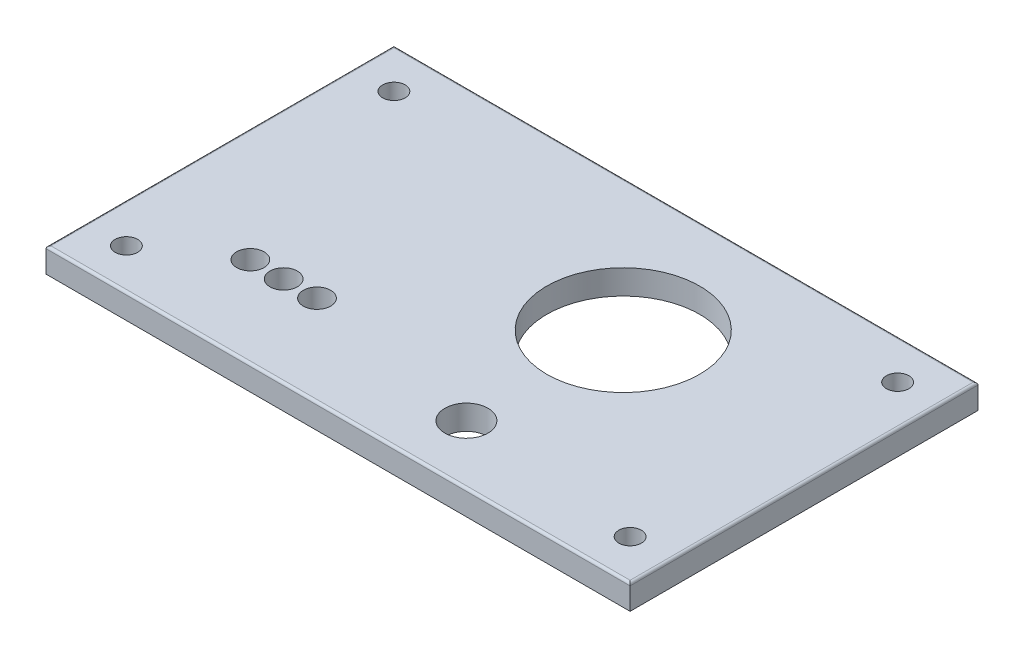
SolidWorks part; units mm, degrees
ref_plane "Front Plane" through (0, 0, 0) normal (0, 0, 1) x (1, 0, 0)
ref_plane "Top Plane" through (0, 0, 0) normal (0, 1, 0) x (1, 0, 0)
ref_plane "Right Plane" through (0, 0, 0) normal (1, 0, 0) x (0, 0, -1)
sketch "Sketch1" plane through (0, 0, 0) normal (0, 1, 0) x (1, 0, 0)
  line L0 (29.8, 17.75) -> (29.8, 15.25) construction
  line L1 (-29.8, -17.75) -> (29.8, -17.75)
  line L2 (-29.8, -17.75) -> (-29.8, 17.75)
  line L3 (-29.8, 17.75) -> (29.8, 17.75)
  line L4 (29.8, -17.75) -> (29.8, 17.75)
  line L5 (-29.8, -17.75) -> (29.8, 17.75) construction
  line L6 (-29.8, 17.75) -> (29.8, -17.75) construction
  line L7 (29.8, 15.25) -> (27.3, 15.25) construction
  line L8 (27.3, 15.25) -> (27.3, 17.75) construction
  line L9 (-4.7, 4.25) -> (-0.7, 4.25) construction
  line L10 (27.3, 15.25) -> (-4.7, 15.25) construction
  line L11 (27.3, 15.25) -> (27.3, -6.75) construction
  line L12 (27.3, -6.75) -> (-4.7, -6.75) construction
  line L13 (-4.7, 15.25) -> (-4.7, -6.75)
  line L14 (-0.7, 4.25) -> (7.1, 4.25) construction
  line L15 (7.1, 4.25) -> (7.1, -6.75) construction
  line L16 (7.1, -6.75) -> (7.1, -9.25) construction
  line L17 (7.1, -9.25) -> (7.1, -14.25) construction
  line L18 (-4.7, 4.25) -> (-7.2, 4.25) construction
  line L19 (-7.2, 4.25) -> (-22.3, 4.25) construction
  line L20 (-14.75, 4.25) -> (-14.75, 18.55) construction
  line L21 (-14.75, 18.55) -> (-7.2, 18.55)
  line L22 (-14.75, 18.55) -> (-22.3, 18.55) construction
  line L23 (-22.3, -8.55) -> (-7.2, -8.55) construction
  line L24 (-22.3, 18.55) -> (-7.2, 18.55) construction
  line L25 (-22.3, 18.55) -> (-22.3, -6.55) construction
  line L26 (-22.3, -6.55) -> (-7.2, -6.55) construction
  line L27 (-7.2, 18.55) -> (-7.2, -6.55) construction
  line L28 (-13.35, -8.55) -> (-12.75, -8.55) construction
  line L29 (-12.75, -8.55) -> (-11.35, -8.55) construction
  line L30 (-16.15, -8.55) -> (-16.75, -8.55) construction
  line L31 (-16.75, -8.55) -> (-18.15, -8.55) construction
  circle A0 centre (7.1, 4.25) radius 7.8
  circle A1 centre (7.1, -11.75) radius 2.2
  circle A2 centre (-14.75, -8.55) radius 1.4
  circle A3 centre (-11.35, -8.55) radius 1.4
  circle A4 centre (-18.15, -8.55) radius 1.4
  point P0 (0, 0)
  dimension "D9" = 15.6
  dimension "D11" = 5
  dimension "D12" = 4.4
  dimension "D20" = 2.8
  dimension "D23" = 2.8
  dimension "D26" = 2.8
  dimension "D1" = 35.5
  dimension "D2" = 59.6
  dimension "D3" = 2.5
  dimension "D4" = 2.5
  dimension "D5" = 32
  dimension "D6" = 22
  dimension "D7" = 4
  dimension "D8" = 7.8
  dimension "D10" = 2.5
  dimension "D13" = 2.5
  dimension "D14" = 15.1
  dimension "D15" = 7.55
  dimension "D16" = 7.55
  dimension "D17" = 25.1
  dimension "D18" = 15.1
  dimension "D21" = 0.6
  dimension "D22" = 1.4
  dimension "D24" = 0.6
  dimension "D25" = 1.4
  dimension "D19" = 2
extrude "Boss-Extrude3" add sketch "Sketch1" along normal blind 2.5 contours L1 L4 L3 L2 A4 A3 A2 A1 A0 region at (-0.6306, 0, 0.2516)
sketch "Sketch6" plane through (0, 2.5, 0) normal (0, 1, 0) x (1, 0, 0)
  line L0 (-21.6, 13.65) -> (-29.8, 13.65) construction
  line L1 (-29.8, 17.75) -> (-21.6, 17.75) construction
  line L2 (-29.8, 17.75) -> (-29.8, 9.55) construction
  line L3 (-29.8, 9.55) -> (-21.6, 9.55) construction
  line L4 (-21.6, 17.75) -> (-21.6, 9.55) construction
  line L5 (0, 17.75) -> (0, 27.4316) construction
  line L6 (-29.8, 17.75) -> (29.8, 17.75) construction
  line L7 (0, 0) -> (0, -20.8453) construction
  line L8 (0, 0) -> (29.8, 0) construction
  line L9 (29.8, -17.75) -> (29.8, 17.75) construction
  line L10 (29.8, 0) -> (50.1979, 0) construction
  circle A0 centre (-25.7, 13.65) radius 1.15
  circle A1 centre (25.7, 13.65) radius 1.15
  circle A2 centre (25.7, -13.65) radius 1.15
  circle A3 centre (-25.7, -13.65) radius 1.15
  dimension "D1" = 8.2
  dimension "D2" = 8.2
extrude "Cut-Extrude4" cut sketch "Sketch6" against normal blind 5
fillet "Fillet4" radius 0.25 4 edges at (29.8, 2.5, 0) (-29.8, 2.5, 0) (0, 2.5, 17.75) (0, 2.5, -17.75)
